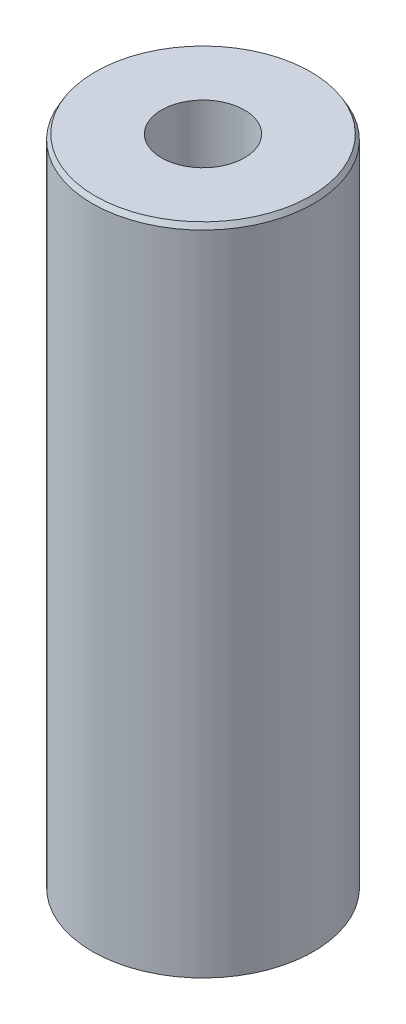
SolidWorks part; units mm, degrees
ref_plane "Front Plane" through (0, 0, 0) normal (0, 0, 1) x (1, 0, 0)
ref_plane "Top Plane" through (0, 0, 0) normal (0, 1, 0) x (1, 0, 0)
ref_plane "Right Plane" through (0, 0, 0) normal (1, 0, 0) x (0, 0, -1)
sketch "Sketch1" plane through (0, 0, 0) normal (0, 1, 0) x (1, 0, 0)
  circle A0 centre (0, 0) radius 55
  dimension "SHAFT_OD" = 110
extrude "Boss-Extrude1" add sketch "Sketch1" along normal blind 326.0058
sketch "Sketch2" plane through (0, 0, 0) normal (0, 1, 0) x (1, 0, 0)
  circle A0 centre (0, 0) radius 20.6295
  dimension "BORE_D" = 41.259
extrude "Cut-Extrude1" cut sketch "Sketch2" along normal through all
chamfer "Chamfer1" distance 2.5274 angle 30 2 edges at (0, 326.0058, 55) (0, 0, 55) first distance on face at (0, 326.0058, 55) first distance on face at (0, 0, 20.6295)
